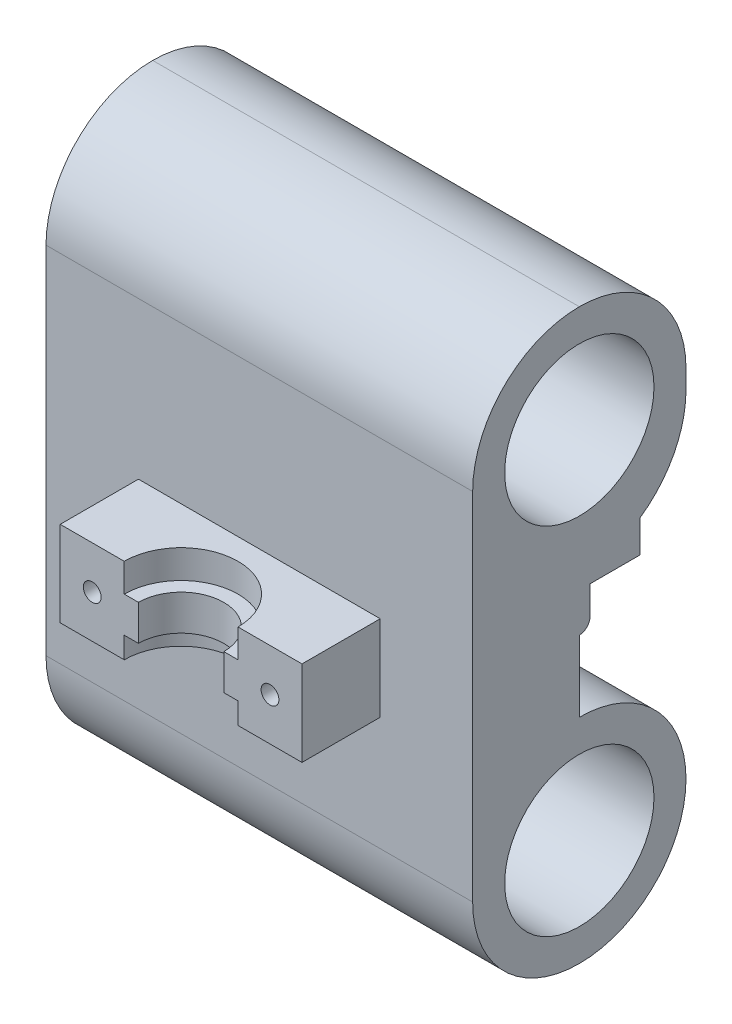
SolidWorks part; units mm, degrees
ref_plane "Спереди" through (0, 0, 0) normal (0, 0, 1) x (1, 0, 0)
ref_plane "Сверху" through (0, 0, 0) normal (0, 1, 0) x (1, 0, 0)
ref_plane "Справа" through (0, 0, 0) normal (1, 0, 0) x (0, 0, -1)
sketch "Эскиз1" plane through (0, 0, 0) normal (1, 0, 0) x (0, 0, -1)
  line L0 (0, 0) -> (0, 80)
  line L1 (0, 80) -> (30, 80)
  line L2 (30, 80) -> (30, 50)
  line L3 (16.5, 40) -> (15, 40)
  line L4 (15, 40) -> (15, 30)
  line L5 (15, 30) -> (30, 30)
  line L6 (30, 30) -> (30, 0)
  line L7 (30, 0) -> (0, 0)
  line L8 (15, 65) -> (15, 15) construction
  line L11 (16.5, 45.5) -> (23.5, 45.5)
  line L12 (16.5, 45.5) -> (16.5, 40)
  line L13 (30, 50) -> (23.5, 50)
  line L14 (23.5, 50) -> (23.5, 45.5)
  circle A0 centre (15, 15) radius 10.5
  circle A1 centre (15, 65) radius 10.5
  point P13 (0, 40)
  point P15 (0, 0)
  dimension "D4" = 21
  dimension "D6" = 21
  dimension "D2" = 15
  dimension "D3" = 15
  dimension "D5" = 30
  dimension "D7" = 15
  dimension "D8" = 50
  dimension "D9" = 15
  dimension "D10" = 1.5
  dimension "D13" = 15
  dimension "D14" = 19.5
  dimension "D15" = 8.5
  dimension "D16" = 15
extrude "Бобышка-Вытянуть2" add sketch "Эскиз1" along normal blind 60
fillet "Скругление1" radius 15 1 edges at (30, 30, -30)
fillet "Скругление5" radius 15 1 edges at (30, 80, -30)
fillet "Скругление3" radius 15 1 edges at (30, 0, -30)
sketch "Эскиз2" plane through (0, 0, 0) normal (0, 0, 1) x (1, 0, 0)
  line L0 (13, 31) -> (13, 43)
  line L2 (13, 43) -> (47, 43)
  line L3 (47, 43) -> (47, 31)
  line L4 (47, 31) -> (13, 31)
  line L5 (60, 0) -> (0, 0) construction
  point P4 (30, 31)
  point P7 (30, 0)
  dimension "D1" = 31
  dimension "D2" = 12
  dimension "D3" = 34
extrude "Бобышка-Вытянуть3" add sketch "Эскиз2" along normal blind 11
sketch "Эскиз3" plane through (0, 43, 0) normal (0, 1, 0) x (1, 0, 0)
  line L0 (47, -11) -> (13, -11) construction
  line L1 (24, -11) -> (36, -11)
  line L2 (36, -11) -> (36.0417, -10.8799)
  arc A0 (36, -11) -> (24, -11) centre (30, -11) ccw
  line M3 (13, -11) -> (47, -11)
  dimension "D1" = 12
extrude "Вырез-Вытянуть1" cut sketch "Эскиз3" against normal up to surface (12 mm away) contours A0 M3 region at (30, 43, 8.4535) up to face at (30, 31, 5.5)
sketch "Эскиз4" plane through (0, 43, 0) normal (0, 1, 0) x (1, 0, 0)
  line L0 (47, -11) -> (36, -11) construction
  line L1 (24, -11) -> (13, -11) construction
  arc A0 (38, -11) -> (22, -11) centre (30, -11) ccw
  arc A1 (36, -11) -> (24, -11) centre (30, -11) ccw construction
  point P11 (30, -5)
  dimension "D1" = 16
extrude "Вырез-Вытянуть2" cut sketch "Эскиз4" against normal blind 4 and the other way through all
sketch "Эскиз5" plane through (0, 31, 0) normal (0, -1, 0) x (-1, 0, 0)
  line L0 (-13, -11) -> (-24, -11) construction
  line L1 (-36, -11) -> (-47, -11) construction
  arc A0 (-22, -11) -> (-38, -11) centre (-30, -11) ccw
  arc A1 (-24, -11) -> (-36, -11) centre (-30, -11) ccw construction
  point P11 (-30, -5)
  dimension "D1" = 16
extrude "Вырез-Вытянуть3" cut sketch "Эскиз5" against normal blind 3 and the other way through all
sketch "Эскиз6" plane through (0, 0, 11) normal (0, 0, 1) x (1, 0, 0)
  line L0 (13, 43) -> (13, 31) construction
  line L1 (47, 31) -> (47, 43) construction
  line L2 (47, 37) -> (12.8652, 37) construction
  circle A0 centre (17.5, 37) radius 1.25
  circle A1 centre (42.5, 37) radius 1.25
  dimension "D1" = 2.5
  dimension "D2" = 2.5
  dimension "D3" = 4.5
  dimension "D4" = 4.5
extrude "Вырез-Вытянуть4" cut sketch "Эскиз6" against normal up to vertex (11 mm away) up to point (13, 31, 0)
fillet "Скругление10" radius 15 1 edges at (30, 80, 0)
fillet "Скругление11" radius 15 1 edges at (30, 0, 0)
fillet "Скругление12" radius 1.5 1 edges at (30, 40, -16.5)
fillet "Скругление13" radius 15 1 edges at (30, 50, -30)
